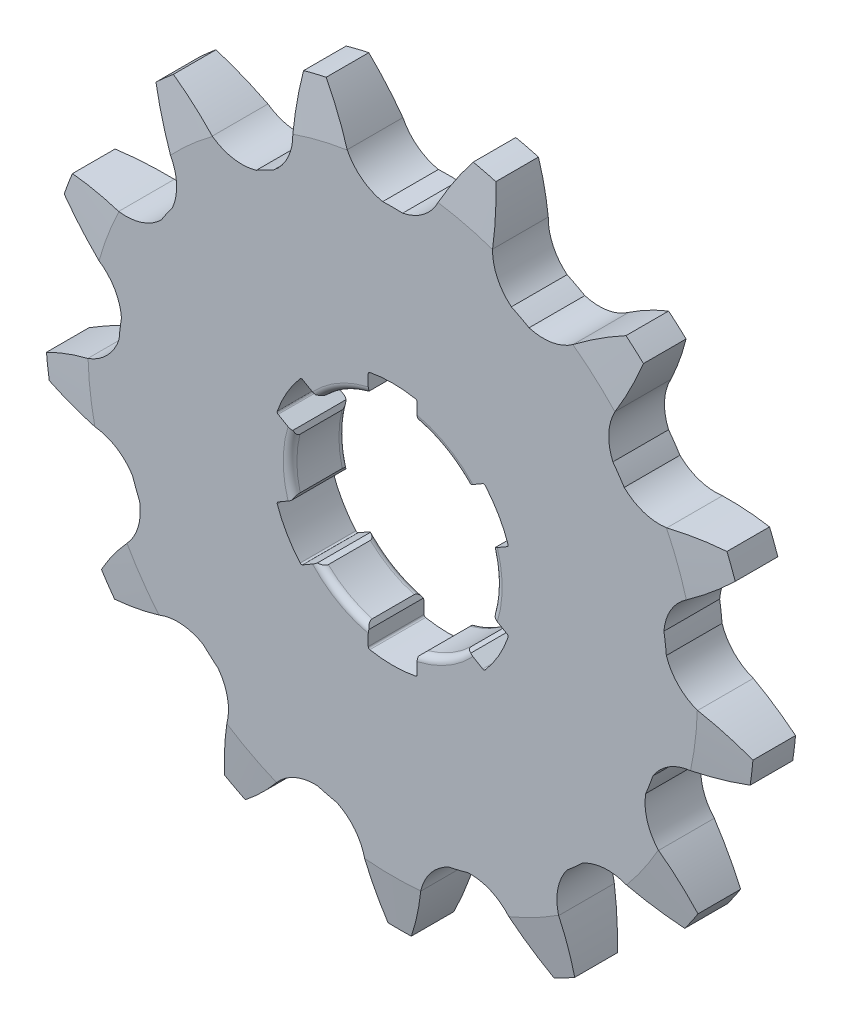
SolidWorks part; units mm, degrees
material "Stal nierdzewna do obróbki plastycznej"
ref_plane "Płaszczyzna XY" through (0, 0, 0) normal (0, 0, 1) x (1, 0, 0)
ref_plane "Płaszczyzna XZ" through (0, 0, 0) normal (0, 1, 0) x (1, 0, 0)
ref_plane "Płaszczyzna YZ" through (0, 0, 0) normal (1, 0, 0) x (0, 0, -1)
sketch "Szkic1" plane through (0, 0, 0) normal (0, 0, 1) x (1, 0, 0)
  line L0 (0, 0) -> (0, 138.6783) construction
  line L1 (0, 0) -> (-31.5593, 128.041) construction
  line L2 (0, 0) -> (31.7367, 128.7607) construction
  line L3 (0, 33.1675) -> (-127.785, -30.5437) construction
  line L4 (0, 33.1675) -> (35.4084, 15.5135) construction
  line L5 (8.6795, 35.2141) -> (6.7218, 27.2713)
  line L6 (-8.6795, 35.2141) -> (-6.7218, 27.2713)
  circle A0 centre (0, 0) radius 28.0875
  circle A1 centre (0, 0) radius 33.1675
  circle A2 centre (0, 0) radius 36.268
  circle A3 centre (0, 33.1675) radius 5.2
  arc A4 (-7.5162, 35.4806) -> (-4.6537, 30.8473) centre (-31.5017, 17.4613) cw
  arc A5 (4.6537, 30.8473) -> (7.5162, 35.4806) centre (31.5017, 17.4613) cw
  dimension "D1" = 56.175
  dimension "D2" = 66.335
  dimension "D3" = 72.536
  dimension "D6" = 10.4
  dimension "D9" = 30
  dimension "D4" = 13.846
  dimension "D5" = 27.692
  dimension "D7" = 127
  dimension "D8" = 63.5
extrude "Dodanie-wyciągnięcie1" add sketch "Szkic1" along normal blind 5.7 contours A4 A1 L6 A0 A3 | A5 A3 A0 L5 A1 | A5 A1 L5 A2 | A4 A2 L6 A1 | A3 A0
pattern_circular "Szyk kołowy1" count 13 over 360 about axis through (0, 0, 0) along (0, 0, 1) of "Dodanie-wyciągnięcie1"
ref_plane "Płaszczyzna1" through (0, 0, 5.7) normal (0, 0, 1) x (1, 0, 0)
sketch "Szkic4" plane through (0, 0, 5.7) normal (0, 0, 1) x (1, 0, 0)
  circle A0 centre (0, 0) radius 31.1675
  dimension "D1" = 62.335
extrude "Wytnij-wyciągnięcie4" cut sketch "Szkic4" against normal blind 35.7 draft 82 flip side to cut contours A0
sketch "Szkic5" plane through (0, 0, 0) normal (0, 0, -1) x (-1, 0, 0)
  circle A0 centre (0, 0) radius 31.1675
  dimension "D1" = 62.335
extrude "Wytnij-wyciągnięcie5" cut sketch "Szkic5" against normal blind 25.7 draft 83 flip side to cut contours A0
sketch "Szkic10" plane through (0, 0, 5.7) normal (0, 0, 1) x (1, 0, 0)
  line L0 (0, 0) -> (0, 17.0782) construction
  line L1 (9.3566, 8.2888) -> (7.5818, 7.2641)
  line L3 (-2.5, 12.2474) -> (-2.5, 10.198)
  line L5 (2.5, 12.2474) -> (2.5, 10.198)
  line L6 (-2.5, 13.3438) -> (2.5, 7.6562) construction
  line L7 (-2.5, 7.6562) -> (2.5, 13.3438) construction
  line L8 (11.8566, 3.9587) -> (10.0818, 2.934)
  line L9 (11.8566, -3.9587) -> (10.0818, -2.934)
  line L10 (9.3566, -8.2888) -> (7.5818, -7.2641)
  line L11 (2.5, -12.2474) -> (2.5, -10.198)
  line L12 (-2.5, -12.2474) -> (-2.5, -10.198)
  line L13 (-9.3566, -8.2888) -> (-7.5818, -7.2641)
  line L14 (-11.8566, -3.9587) -> (-10.0818, -2.934)
  line L15 (-11.8566, 3.9587) -> (-10.0818, 2.934)
  line L16 (-9.3566, 8.2888) -> (-7.5818, 7.2641)
  circle A0 centre (0, 0) radius 12.5
  circle A1 centre (0, 0) radius 10.5
  point P4 (0, 10.5)
  point P36 (0, 0)
  circle M4 centre (0, 0) radius 12.5
  dimension "D1" = 25
  dimension "D2" = 21
  dimension "D3" = 5
  dimension "D4" = 6
extrude "Wytnij-wyciągnięcie6" cut sketch "Szkic10" against normal through all contours A1 | A1 L16 L15 M4 | A1 L14 L13 M4 | A1 L12 L11 M4 | A1 L10 L9 M4 | A1 L8 L1 M4 | A1 L5 L3 M4
fillet "Zaokrąglenie1" radius 0.2 12 edges at (-11.8566, 3.9587, 2.85) (-11.8566, -3.9587, 2.85) (-9.3566, -8.2888, 2.85) (-2.5, -12.2474, 2.85) (2.5, -12.2474, 2.85) (9.3566, -8.2888, 2.85) (11.8566, -3.9587, 2.85) (11.8566, 3.9587, 2.85) (9.3566, 8.2888, 2.85) (2.5, 12.2474, 2.85) (-2.5, 12.2474, 2.85) (-9.3566, 8.2888, 2.85)
chamfer "Sfazowanie1" distance 0.3 angle 45 12 edges at (2.5, -10.198, 2.85) (7.5818, -7.2641, 2.85) (10.0818, -2.934, 2.85) (10.0818, 2.934, 2.85) (7.5818, 7.2641, 2.85) (2.5, 10.198, 2.85) (-2.5, 10.198, 2.85) (-7.5818, 7.2641, 2.85) (-10.0818, 2.934, 2.85) (-7.5818, -7.2641, 2.85) (-10.0818, -2.934, 2.85) (-2.5, -10.198, 2.85)
fillet "Zaokrąglenie3" radius 0.7 12 edges at (10.4998, 0.0595, 0) (5.1984, 9.1229, 0) (-10.4998, -0.0595, 0) (-5.1984, -9.1229, 0) (5.3014, -9.0634, 0) (-5.3014, 9.0634, 0) (-10.4998, -0.0595, 5.7) (-5.1984, -9.1229, 5.7) (-5.3014, 9.0634, 5.7) (5.1984, 9.1229, 5.7) (10.4998, 0.0595, 5.7) (5.3014, -9.0634, 5.7)
equation "\"df\"= 56.175mm"
equation "\"D1@Szkic1\"= \"df\""
equation "\"d\"= 66.335mm"
equation "\"D2@Szkic1\"=\"d\""
equation "\"da\"= 72.536mm"
equation "\"D3@Szkic1\"= \"da\""
equation "\"alfa\"= 127stopnie"
equation "\"D4@Szkic1\"= 360 / ( 2 * \"z\" )"
equation "\"z\"= 13"
equation "\"D5@Szkic1\"= 360 / \"z\""
equation "\"ri\"= 5.2"
equation "\"D6@Szkic1\"= \"ri\" * 2"
equation "\"D7@Szkic1\"= \"alfa\""
equation "\"D8@Szkic1\"= \"alfa\" / 2"
equation "\"re\"= 30"
equation "\"D9@Szkic1\"=\"re\""
equation "\"D1@Szyk kołowy1\"= \"z\""
equation "\"D1@Szkic5\"= \"d\" - 4"
equation "\"D1@Szkic4\"= \"d\" - 4"
